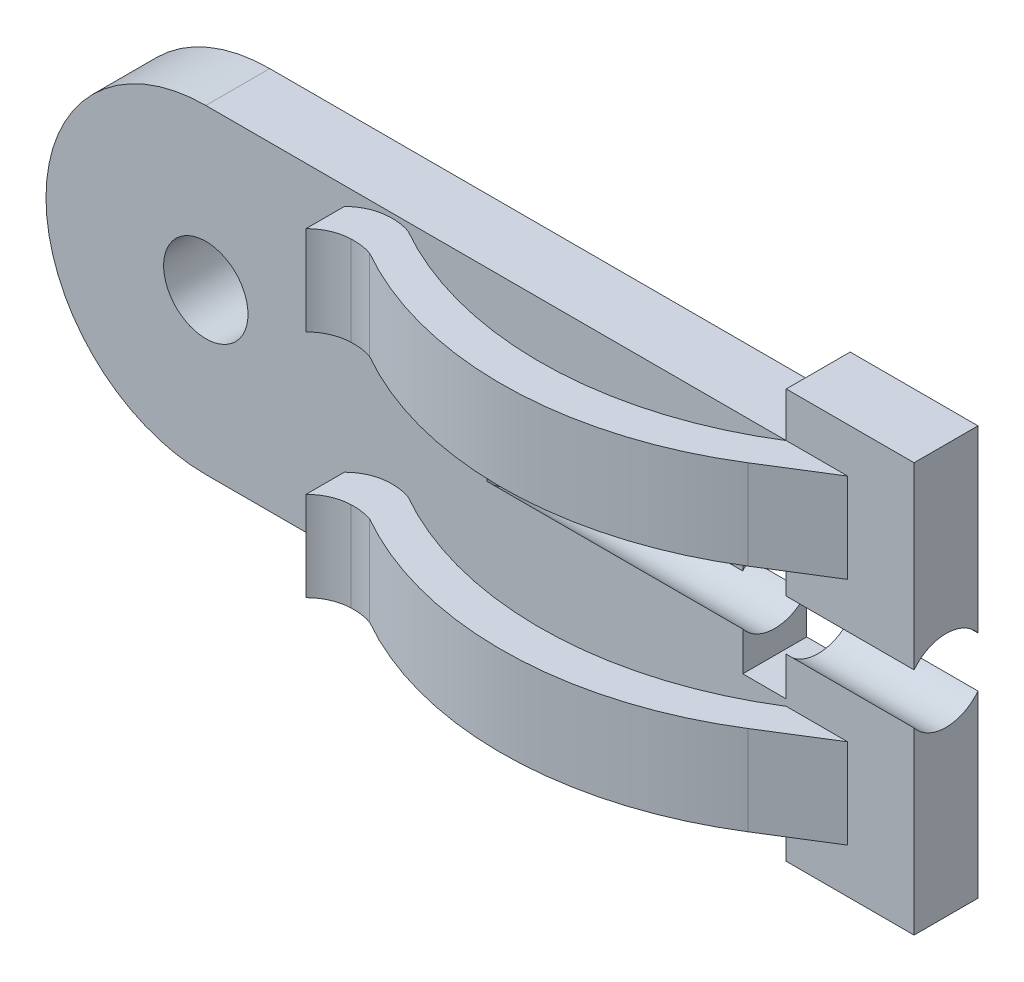
SolidWorks part; units mm, degrees
ref_plane "Front Plane" through (0, 0, 0) normal (0, 0, 1) x (1, 0, 0)
ref_plane "Top Plane" through (0, 0, 0) normal (0, 1, 0) x (1, 0, 0)
ref_plane "Right Plane" through (0, 0, 0) normal (1, 0, 0) x (0, 0, -1)
sketch "Sketch1" plane through (0, 0, 0) normal (0, 0, 1) x (1, 0, 0)
  line L0 (0, -6.25) -> (22.7, -6.25)
  line L1 (-12.7, 12.7) -> (12.7, 12.7)
  line L2 (-12.7, 12.7) -> (-12.7, -12.7)
  line L3 (-12.7, -12.7) -> (12.7, -12.7)
  line L4 (12.7, 12.7) -> (12.7, -12.7)
  line L5 (0, 6.25) -> (22.7, 6.25)
  line L6 (22.7, 6.25) -> (22.7, -6.25)
  circle A0 centre (0, 0) radius 1.65
  arc A1 (0, 6.25) -> (0, -6.25) centre (0, 0) ccw
  dimension "D1" = 3.3
  dimension "D3" = 25.4
  dimension "D4" = 25.4
  dimension "D5" = 12.7
  dimension "D6" = 12.7
  dimension "D7" = 10
extrude "Boss-Extrude1" add sketch "Sketch1" along normal blind 2.5 contours L5 A1 L0 L4 A0 | L6 L5 L4 L0 region at (3.9956, 0, 0) region at (17.7, 0, 0)
sketch "Sketch2" plane through (0, 0, 2.5) normal (0, 0, 1) x (1, 0, 0)
  line L1 (22.7, -8) -> (27.7, -8)
  line L2 (22.7, -8) -> (22.7, 8)
  line L3 (22.7, 8) -> (27.7, 8)
  line L4 (27.7, -8) -> (27.7, 8)
  circle A0 centre (0, 0) radius 1.65 construction
  dimension "D1" = 5
  dimension "D2" = 16
  dimension "D3" = 8
extrude "Boss-Extrude2" add sketch "Sketch2" against normal blind 2.5
sketch "Sketch3" plane through (0, 0, 2.5) normal (0, 0, 1) x (1, 0, 0)
  line L0 (22.7, 8) -> (22.7, 6.25) construction
  line L1 (22.7, 2.5) -> (21, 2.5)
  line L2 (22.7, 2.5) -> (22.7, -2.5)
  line L3 (22.7, -2.5) -> (21, -2.5)
  line L4 (21, 2.5) -> (21, -2.5)
  circle A0 centre (0, 0) radius 1.65 construction
  dimension "D1" = 1.7
  dimension "D2" = 0
  dimension "D3" = 5
  dimension "D4" = 2.5
extrude "Cut-Extrude1" cut sketch "Sketch3" against normal through all
sketch "Sketch6" plane through (27.7, 0, 0) normal (1, 0, 0) x (0, 0, -1)
  line L0 (-2.5, -8) -> (-2.5, 8) construction
  line L1 (0, -8) -> (-2.5, -8) construction
  line L2 (0, 8) -> (-2.5, 8) construction
  circle A0 centre (-1.25, 0) radius 1.59
  point P6 (-1.25, 8)
  dimension "D4" = 3.18
  dimension "D1" = 1.25
  dimension "D2" = 8
  dimension "D3" = 8
extrude "Cut-Extrude3" cut sketch "Sketch6" against normal blind 16.7
sketch "Sketch7" plane through (0, -6.25, 0) normal (0, -1, 0) x (1, 0, 0)
  line L1 (6.1299, 3.2107) -> (6.1299, 4.7107)
  line L3 (22.7, 4) -> (22.7, 2.5)
  arc A0 (22.7, 2.5) -> (8.2067, 2.7997) centre (15.2027, -9.4701) ccw
  arc A1 (7.3606, 2.6809) -> (6.1299, 3.2107) centre (7.409, 4.4878) cw
  arc A2 (7.3606, 2.6809) -> (8.2067, 2.7997) centre (7.4758, 4.9321) ccw
  arc A3 (7.3606, 4.1809) -> (6.1299, 4.7107) centre (7.409, 5.9878) cw
  arc A4 (22.7, 4) -> (8.2067, 4.2997) centre (15.2027, -7.9701) ccw
  arc A5 (7.3606, 4.1809) -> (8.2067, 4.2997) centre (7.4758, 6.4321) ccw
  dimension "D3" = 2
  dimension "D1" = 1.5
extrude "Boss-Extrude3" add sketch "Sketch7" against normal blind 3.5 separate body
sketch "Sketch9" plane through (0, -6.25, 0) normal (0, -1, 0) x (1, 0, 0)
  line L0 (22.7, 4) -> (25.1049, 2.5)
  line L1 (25.1049, 2.5) -> (22.7, 2.5)
  line L2 (22.7, 2.5) -> (22.7, 4)
extrude "Boss-Extrude5" add sketch "Sketch9" against normal blind 3.5 separate body
combine bodies "Combine1" operation type add bodies to combine 111 106
ref_plane "Plane1" through (0, 0, 0) normal (0, -1, 0) x (-1, 0, 0)
mirror "Mirror5" about plane through (0, 0, 0) normal (0, -1, 0) of bodies 112
combine bodies "Combine4" operation type add bodies to combine 105 112 116
